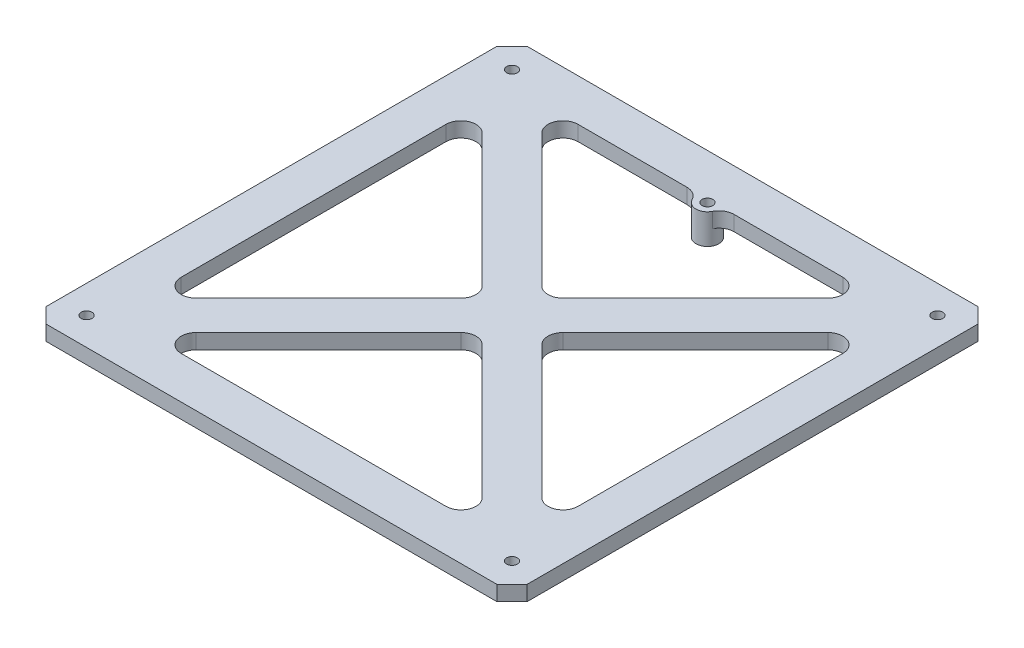
SolidWorks part; units mm, degrees
ref_plane "Front Plane" through (0, 0, 0) normal (0, 0, 1) x (1, 0, 0)
ref_plane "Top Plane" through (0, 0, 0) normal (0, 1, 0) x (1, 0, 0)
ref_plane "Right Plane" through (0, 0, 0) normal (1, 0, 0) x (0, 0, -1)
sketch "Sketch1" plane through (0, 0, 0) normal (0, 1, 0) x (1, 0, 0)
  line L0 (0, 196.85) -> (6.35, 203.2)
  line L1 (6.35, 0) -> (196.85, 0)
  line L2 (0, 6.35) -> (0, 196.85)
  line L3 (6.35, 203.2) -> (196.85, 203.2)
  line L4 (203.2, 6.35) -> (203.2, 196.85)
  line L5 (196.85, 203.2) -> (203.2, 196.85)
  line L6 (196.85, 0) -> (203.2, 6.35)
  line L7 (0, 6.35) -> (6.35, 0)
  point P0 (0, 0)
  point P1 (203.2, 203.2)
  point P2 (0, 203.2)
  point P3 (203.2, 0)
  dimension "D1" = 203.2
  dimension "D2" = 203.2
extrude "Boss-Extrude1" add sketch "Sketch1" along normal blind 6.35
sketch "Sketch2" plane through (0, 6.35, 0) normal (0, 1, 0) x (1, 0, 0)
  line L0 (203.2, 6.35) -> (203.2, 196.85) construction
  line L1 (45.6826, 185.42) -> (157.5174, 185.42)
  line L2 (17.78, 157.5174) -> (17.78, 45.6826)
  line L3 (45.6826, 17.78) -> (157.5174, 17.78)
  line L4 (185.42, 157.5174) -> (185.42, 45.6826)
  line L5 (196.85, 203.2) -> (6.35, 203.2) construction
  line L6 (0, 196.85) -> (0, 6.35) construction
  line L7 (3.175, 3.175) -> (200.025, 200.025) construction
  line L8 (3.175, 200.025) -> (101.6, 101.6) construction
  line L9 (28.6201, 162.0075) -> (84.5375, 106.0901)
  line L10 (41.1925, 28.6201) -> (97.1099, 84.5375)
  line L11 (41.1925, 174.5799) -> (97.1099, 118.6625)
  line L12 (28.6201, 41.1925) -> (84.5375, 97.1099)
  line L13 (9.4612, -3.1112) -> (206.3112, 193.7388) construction
  line L14 (-3.1112, 9.4612) -> (193.7388, 206.3112) construction
  line L15 (9.4612, 206.3112) -> (206.3112, 9.4612) construction
  line L16 (-3.1112, 193.7388) -> (193.7388, -3.1112) construction
  line L17 (118.6625, 106.0901) -> (174.5799, 162.0075)
  line L18 (101.6, 101.6) -> (200.025, 3.175) construction
  line L19 (3.175, 200.025) -> (200.025, 3.175) construction
  line L20 (118.6625, 97.1099) -> (174.5799, 41.1925)
  line L21 (106.0901, 118.6625) -> (162.0075, 174.5799)
  line L22 (106.0901, 84.5375) -> (162.0075, 28.6201)
  line L23 (6.35, 0) -> (196.85, 0) construction
  line L24 (6.35, 203.2) -> (0, 196.85) construction
  line L25 (203.2, 196.85) -> (196.85, 203.2) construction
  line L26 (196.85, 0) -> (203.2, 6.35) construction
  arc A0 (185.42, 45.6826) -> (174.5799, 41.1925) centre (179.07, 45.6826) cw
  arc A1 (185.42, 157.5174) -> (174.5799, 162.0075) centre (179.07, 157.5174) ccw
  arc A2 (157.5174, 185.42) -> (162.0075, 174.5799) centre (157.5174, 179.07) cw
  arc A3 (118.6625, 106.0901) -> (118.6625, 97.1099) centre (123.1526, 101.6) ccw
  arc A4 (41.1925, 28.6201) -> (45.6826, 17.78) centre (45.6826, 24.13) ccw
  arc A5 (157.5174, 17.78) -> (162.0075, 28.6201) centre (157.5174, 24.13) ccw
  arc A6 (28.6201, 41.1925) -> (17.78, 45.6826) centre (24.13, 45.6826) cw
  arc A7 (84.5375, 97.1099) -> (84.5375, 106.0901) centre (80.0474, 101.6) ccw
  arc A8 (28.6201, 162.0075) -> (17.78, 157.5174) centre (24.13, 157.5174) ccw
  arc A9 (41.1925, 174.5799) -> (45.6826, 185.42) centre (45.6826, 179.07) cw
  arc A10 (97.1099, 84.5375) -> (106.0901, 84.5375) centre (101.6, 80.0474) cw
  arc A11 (97.1099, 118.6625) -> (106.0901, 118.6625) centre (101.6, 123.1526) ccw
  point P10 (0, 101.6)
  point P11 (17.78, 101.6)
  point P37 (101.6, 17.78)
  point P40 (101.6, 101.6)
  point P50 (114.1724, 101.6)
  point P65 (101.6, 89.0276)
  point P68 (101.6, 114.1724)
  dimension "D7" = 6.35
  dimension "D8" = 6.35
  dimension "D9" = 6.35
  dimension "D1" = 17.78
  dimension "D2" = 17.78
  dimension "D3" = 8.89
  dimension "D5" = 17.78
  dimension "D6" = 17.78
  dimension "D4" = 8.89
extrude "Cut-Extrude1" cut sketch "Sketch2" against normal through all
sketch "Sketch3" plane through (0, 6.35, 0) normal (0, 1, 0) x (1, 0, 0)
  line L0 (6.35, 0) -> (196.85, 0) construction
  line L1 (0, 196.85) -> (0, 6.35) construction
  line L2 (203.2, 6.35) -> (203.2, 196.85) construction
  line L3 (196.85, 203.2) -> (6.35, 203.2) construction
  circle A0 centre (11.7373, 11.7373) radius 2.286
  circle A1 centre (191.4627, 11.7373) radius 2.286
  circle A2 centre (191.4627, 191.4627) radius 2.286
  circle A3 centre (11.7373, 191.4627) radius 2.286
  dimension "D1" = 2
  dimension "D3" = 4.572
  dimension "D4" = 11.7373
  dimension "D5" = 11.7373
  dimension "D6" = 11.7373
  dimension "D7" = 11.7373
  dimension "D8" = 11.7373
  dimension "D2" = 2
extrude "Cut-Extrude2" cut sketch "Sketch3" against normal through all
sketch "Sketch4" plane through (0, 6.35, 0) normal (0, 1, 0) x (1, 0, 0)
  line L0 (196.85, 203.2) -> (6.35, 203.2) construction
  line L1 (157.5174, 185.42) -> (45.6826, 185.42) construction
  line L3 (111.5547, 185.42) -> (91.6453, 185.42)
  circle A0 centre (101.6, 184.15) radius 2.286 construction
  arc A1 (97.3014, 181.9564) -> (105.8986, 181.9564) centre (101.6, 184.15) ccw
  arc A2 (97.3014, 181.9564) -> (91.6453, 185.42) centre (91.6453, 179.07) ccw
  arc A3 (111.5547, 185.42) -> (105.8986, 181.9564) centre (111.5547, 179.07) ccw
  point P5 (101.6, 203.2)
  dimension "D1" = 19.05
  dimension "D2" = 4.572
  dimension "D3" = 2.54
  dimension "D4" = 12.7
extrude "Boss-Extrude2" add sketch "Sketch4" against normal up to surface (6.35 mm away) up to face at (11.7373, 0, -189.1767)
sketch "Sketch5" plane through (0, 0, 0) normal (0, -1, 0) x (1, 0, 0)
  circle A0 centre (101.6, -184.15) radius 4.826
  arc A1 (105.8986, -181.9564) -> (97.3014, -181.9564) centre (101.6, -184.15) ccw construction
extrude "Boss-Extrude3" add sketch "Sketch5" along normal blind 6.35
sketch "Sketch6" plane through (0, -6.35, 0) normal (0, -1, 0) x (1, 0, 0)
  circle A0 centre (101.6, -184.15) radius 2.286
  dimension "D1" = 4.572
extrude "Cut-Extrude3" cut sketch "Sketch6" against normal through all contours A0
